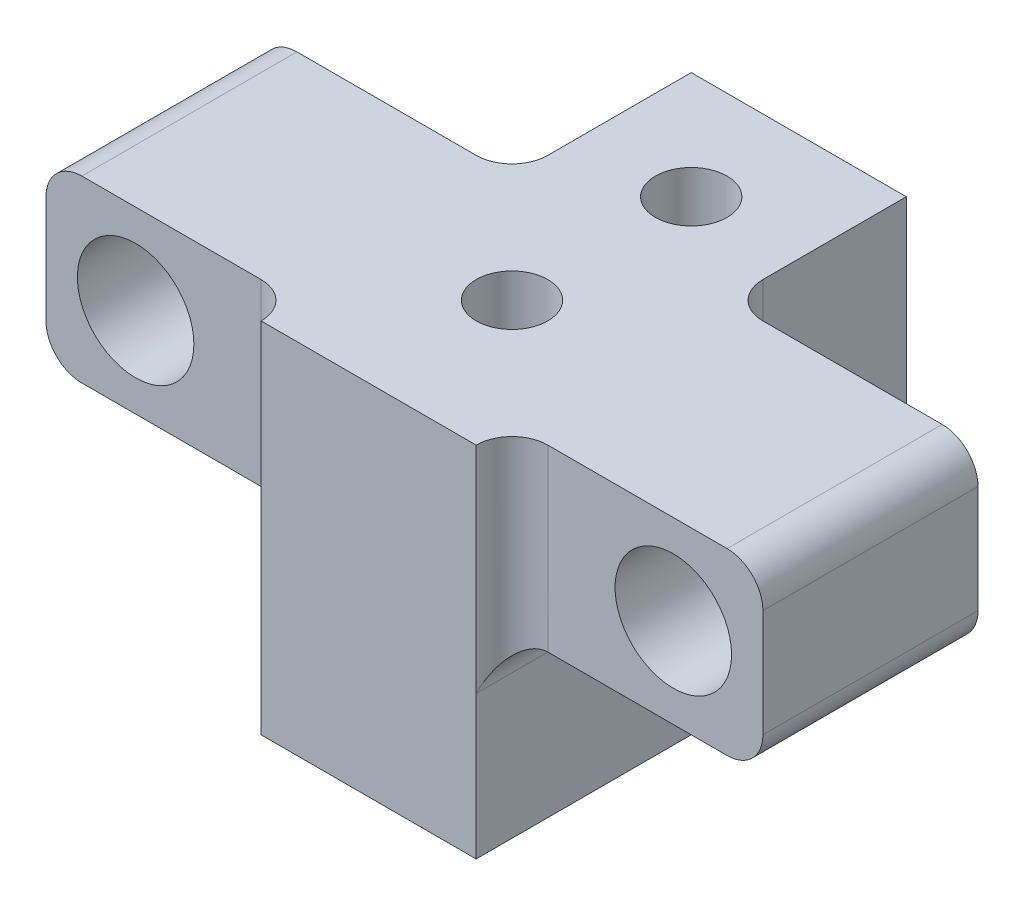
SolidWorks part; units mm, degrees
material "POM Acetal Copolymer"
ref_plane "Front Plane" through (0, 0, 0) normal (0, 0, 1) x (1, 0, 0)
ref_plane "Top Plane" through (0, 0, 0) normal (0, 1, 0) x (1, 0, 0)
ref_plane "Right Plane" through (0, 0, 0) normal (1, 0, 0) x (0, 0, -1)
sketch "Sketch2" plane through (0, 0, 0) normal (0, 1, 0) x (1, 0, 0)
  line L0 (0, -1000) -> (0, 49000) construction
  line L2 (3, -6) -> (-3, -6)
  line L3 (3, -6) -> (3, 6)
  line L4 (3, 6) -> (-3, 6)
  line L5 (-3, -6) -> (-3, 6)
  line L6 (3, -6) -> (-3, 6) construction
  line L7 (-1000, 0) -> (49000, 0) construction
  line L8 (3, 6) -> (-3, -6) construction
  line L9 (-1000, -2) -> (49000, -2) construction
  line L17 (10, -5) -> (-10, -5)
  line L18 (10, -5) -> (10, 1)
  line L19 (10, 1) -> (-10, 1)
  line L20 (-10, -5) -> (-10, 1)
  line L21 (10, -5) -> (-10, 1) construction
  line L22 (10, 1) -> (-10, -5) construction
  point P1 (0, 0)
  point P13 (0, 5)
  point P19 (0, -2)
  dimension "D1" = 6
  dimension "D2" = 12
  dimension "D4" = 2
  dimension "D7" = 20
  dimension "D8" = 6
sketch "Sketch5" [suppressed] plane through (0, 0, 0) normal (0, 0, 1) x (1, 0, 0)
  line L0 (-7.5, 5.8595) -> (-7.5, 2.1204) construction
  line L1 (-11.5, 0) -> (-2.5, 0) construction
  line L3 (-2.5, 7) -> (-11.5, 7)
  line L8 (0, 8.1931) -> (0, -1.2607) construction
  line L9 (-10.7802, 2.5) -> (10.8635, 2.5) construction
  line L11 (-4.5, 3.1305) -> (-4.5, 1.7094) construction
  line L12 (-4.5, 2) -> (-2.5, 2)
  line L13 (-2.5, 2) -> (-2.5, 7)
  line L14 (-11.5, 7) -> (-11.5, 0)
  line L16 (-10, 2.5) -> (-10, 0)
  line L19 (-10, 0) -> (-11.5, 0)
  line L20 (4.5, 3.1305) -> (4.5, 1.7094) construction
  line L21 (7.5, 5.8595) -> (7.5, 2.1204) construction
  line L22 (10, 0) -> (11.5, 0)
  line L23 (10, 2.5) -> (10, 0)
  line L24 (11.5, 7) -> (11.5, 0)
  line L25 (2.5, 2) -> (2.5, 7)
  line L26 (4.5, 2) -> (2.5, 2)
  line L27 (2.5, 7) -> (11.5, 7)
  circle A0 centre (-7.5, 2.5) radius 2.5
  arc A1 (5, 2.5) -> (4.5, 2) centre (4.5, 2.5) cw
  circle A2 centre (-7.5, 2.5) radius 1.55
  circle A3 centre (7.5, 2.5) radius 1.55
  arc A4 (-5, 2.5) -> (-4.5, 2) centre (-4.5, 2.5) ccw
  circle A5 centre (7.5, 2.5) radius 2.5
  point P25 (-10, 0)
  dimension "D3" = 2.5
  dimension "D1" = 7.5
  dimension "D4" = 3
extrude "Boss-Extrude1" add sketch "Sketch2" along normal blind 10 contours L5 | L3 L5 | L3 | L19 L3 L5 | L20 L17 L5 L19 | L3 L17 L5 L2 | L18 L19 L3 L17 | L3 L19 L5 L17 | L3 L4 L5 region at (0, 0, 5.5) region at (0, 0, 2) region at (6.5, 0, 2) region at (-6.5, 0, 2) region at (0, 0, -3.5)
sketch "Sketch6" plane through (0, 0, 0) normal (0, 1, 0) x (1, 0, 0)
  line L0 (-1000, 0) -> (49000, 0) construction
  line L1 (0, -1000) -> (0, 49000) construction
  line L2 (-1010, 3) -> (48990, 3) construction
  line L4 (-1010, -2) -> (48990, -2) construction
  line L5 (-10, -5) -> (-10, 1) construction
  circle A0 centre (0, 3) radius 1
  circle A1 centre (0, -2) radius 1
  point P15 (-10, -2)
  dimension "D1" = 2
  dimension "D2" = 2
  dimension "D3" = 3
extrude "Cut-Extrude2" cut sketch "Sketch6" along normal through all
sketch "Sketch7" plane through (0, 0, 0) normal (0, 0, 1) x (1, 0, 0)
  line L0 (-1000, 0) -> (49000, 0) construction
  line L1 (-1000, 10) -> (49000, 10) construction
  line L2 (3, 10) -> (-3, 10) construction
  line L3 (0, -1000) -> (0, 49000) construction
  line L4 (-3, -1000) -> (-3, 49000) construction
  line L5 (3, -1000) -> (3, 49000) construction
  line L6 (-1006.6853, 7.5) -> (48993.3147, 7.5) construction
  line L7 (-7.5, -993) -> (-7.5, 49007) construction
  line L8 (-10, 0) -> (-3, 0)
  line L9 (-10, 0) -> (-10, 5)
  line L10 (-10, 5) -> (-4, 5)
  line L11 (-3, 0) -> (-3, 4)
  line L13 (7.5, -993) -> (7.5, 49007) construction
  line L15 (3, 0) -> (3, 4)
  line L16 (10, 0) -> (3, 0)
  line L18 (10, 5) -> (4, 5)
  line L19 (10, 0) -> (10, 5)
  circle A0 centre (-7.5, 7.5) radius 1.625
  arc A1 (-4, 5) -> (-3, 4) centre (-4, 4) cw
  arc A2 (4, 5) -> (3, 4) centre (4, 4) ccw
  circle A3 centre (7.5, 7.5) radius 1.625
  point P8 (0, 10)
  point P28 (-3, 5)
  dimension "D1" = 3.25
  dimension "D4" = 1
  dimension "D2" = 2.5
  dimension "D3" = 2.5
  dimension "D5" = 7.5
extrude "Cut-Extrude4" cut sketch "Sketch7" against normal through all and the other way through all
fillet "Fillet1" radius 1 8 edges at (10, 5, 2) (10, 10, 2) (-10, 5, 2) (-10, 10, 2) (-3, 7, 5) (3, 7, 5) (3, 7, -1) (-3, 7, -1)
